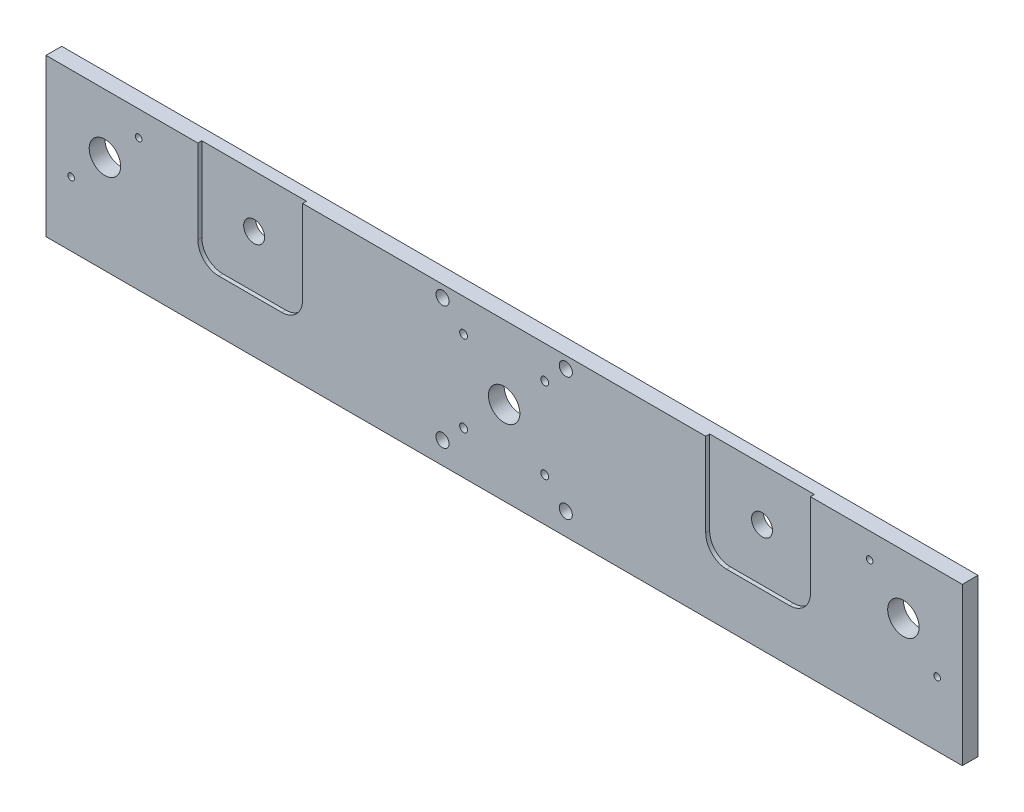
SolidWorks part; units mm, degrees
ref_plane "Alzado" through (0, 0, 0) normal (0, 0, 1) x (1, 0, 0)
ref_plane "Planta" through (0, 0, 0) normal (0, 1, 0) x (1, 0, 0)
ref_plane "Vista lateral" through (0, 0, 0) normal (1, 0, 0) x (0, 0, -1)
sketch "Croquis1" plane through (0, 0, 0) normal (0, 0, 1) x (1, 0, 0)
  line L1 (-350, -60) -> (0, -60)
  line L2 (-350, -60) -> (-350, 0)
  line L3 (-350, 0) -> (0, 0)
  line L4 (0, -60) -> (0, 0)
  dimension "D1" = 350
  dimension "D2" = 60
extrude "Saliente-Extruir1" add sketch "Croquis1" along normal blind 6 contours L3 L4 L1 L2
sketch "Croquis2" plane through (0, 0, 6) normal (0, 0, 1) x (1, 0, 0)
  line L0 (-350, -60) -> (-350, 0) construction
  line L1 (0, -60) -> (0, 0) construction
  line L2 (-350, -60) -> (0, -60) construction
  line L3 (-340.4047, -35.4047) -> (-314.5953, -9.5953) construction
  line L4 (-35.4047, -9.5953) -> (-9.5953, -35.4047) construction
  line L5 (-350, 0) -> (0, 0) construction
  circle A0 centre (-327.5, -22.5) radius 6
  circle A1 centre (-22.5, -22.5) radius 6
  circle A2 centre (-327.5, -22.5) radius 18.25 construction
  circle A4 centre (-314.5953, -9.5953) radius 1.25
  circle A5 centre (-340.4047, -35.4047) radius 1.25
  circle A6 centre (-22.5, -22.5) radius 18.25 construction
  circle A7 centre (-35.4047, -9.5953) radius 1.25
  circle A8 centre (-9.5953, -35.4047) radius 1.25
  circle A9 centre (-22.5, -22.5) radius 21 construction
  circle A10 centre (-327.5, -22.5) radius 21 construction
  dimension "D1" = 12
  dimension "D2" = 12
  dimension "D7" = 36.5
  dimension "D9" = 2.5
  dimension "D10" = 2.5
  dimension "D11" = 36.5
  dimension "D13" = 2.5
  dimension "D14" = 2.5
  dimension "D15" = 42
  dimension "D16" = 42
  dimension "D3" = 22.5
  dimension "D4" = 22.5
  dimension "D5" = 22.5
  dimension "D6" = 22.5
  dimension "D8" = 45
  dimension "D12" = 45
extrude "Cortar-Extruir1" cut sketch "Croquis2" against normal through all
sketch "Croquis3" plane through (0, 0, 6) normal (0, 0, 1) x (1, 0, 0)
  line L3 (-198.55, -51.55) -> (-151.45, -51.55) construction
  line L6 (-198.55, -51.55) -> (-198.55, -4.45) construction
  line L9 (-350, 0) -> (0, 0) construction
  line L10 (-198.55, -4.45) -> (-151.45, -4.45) construction
  line L13 (-151.45, -51.55) -> (-151.45, -4.45) construction
  line L16 (-198.55, -51.55) -> (-151.45, -4.45) construction
  line L21 (-198.55, -4.45) -> (-151.45, -51.55) construction
  line L24 (-190.5, -43.5) -> (-159.5, -43.5) construction
  line L27 (-190.5, -43.5) -> (-190.5, -12.5) construction
  line L30 (-190.5, -12.5) -> (-159.5, -12.5) construction
  line L34 (0, -60) -> (0, 0) construction
  line L35 (-159.5, -43.5) -> (-159.5, -12.5) construction
  line L36 (-190.5, -43.5) -> (-159.5, -12.5) construction
  line L37 (-190.5, -12.5) -> (-159.5, -43.5) construction
  circle A27 centre (-175, -28) radius 6
  circle A28 centre (-190.5, -12.5) radius 1.5
  circle A29 centre (-159.5, -12.5) radius 1.5
  circle A30 centre (-190.5, -43.5) radius 1.5
  circle A31 centre (-151.45, -51.55) radius 2.5
  circle A32 centre (-198.55, -51.55) radius 2.5
  circle A33 centre (-159.5, -43.5) radius 1.5
  circle A34 centre (-151.45, -4.45) radius 2.5
  circle A35 centre (-198.55, -4.45) radius 2.5
  dimension "D5" = 3
  dimension "D9" = 31
  dimension "D41" = 12
  dimension "D1" = 3
  dimension "D2" = 3
  dimension "D3" = 5
  dimension "D10" = 5
  dimension "D11" = 5
  dimension "D12" = 5
  dimension "D13" = 3
  dimension "D6" = 47.1
  dimension "D7" = 47.1
  dimension "D8" = 31
  dimension "D42" = 175
  dimension "D43" = 28
extrude "Cortar-Extruir2" cut sketch "Croquis3" against normal through all
sketch "Croquis5" plane through (0, 0, 6) normal (0, 0, 1) x (1, 0, 0)
  line L0 (-350, 0) -> (0, 0) construction
  line L1 (-292, 0) -> (-252, 0)
  line L2 (-292, 0) -> (-292, -32)
  line L3 (-284, -40) -> (-260, -40)
  line L4 (-252, 0) -> (-252, -32)
  line L5 (-350, -60) -> (-350, 0) construction
  line L6 (-98, 0) -> (-58, 0)
  line L7 (-98, 0) -> (-98, -32)
  line L8 (-90, -40) -> (-66, -40)
  line L9 (-58, 0) -> (-58, -32)
  line L10 (0, -60) -> (0, 0) construction
  arc A0 (-260, -40) -> (-252, -32) centre (-260, -32) ccw
  arc A1 (-284, -40) -> (-292, -32) centre (-284, -32) cw
  arc A2 (-66, -40) -> (-58, -32) centre (-66, -32) ccw
  arc A3 (-90, -40) -> (-98, -32) centre (-90, -32) cw
  point P11 (-252, -40)
  dimension "D4" = 8
  dimension "D6" = 8
  dimension "D1" = 40
  dimension "D2" = 58
  dimension "D3" = 40
  dimension "D5" = 40
  dimension "D7" = 58
  dimension "D8" = 40
extrude "Cortar-Extruir4" cut sketch "Croquis5" against normal blind 1.5
sketch "Croquis7" plane through (0, 0, 4.5) normal (0, 0, 1) x (1, 0, 0)
  line L0 (-252, -32) -> (-252, 0) construction
  line L1 (-252, 0) -> (-292, 0) construction
  line L3 (-58, -32) -> (-58, 0) construction
  line L4 (-58, 0) -> (-98, 0) construction
  circle A0 centre (-272, -20) radius 4
  circle A1 centre (-78, -20) radius 4
  dimension "D1" = 8
  dimension "D4" = 8
  dimension "D5" = 20
  dimension "D2" = 20
  dimension "D3" = 20
  dimension "D6" = 20
extrude "Cortar-Extruir5" cut sketch "Croquis7" against normal through all
